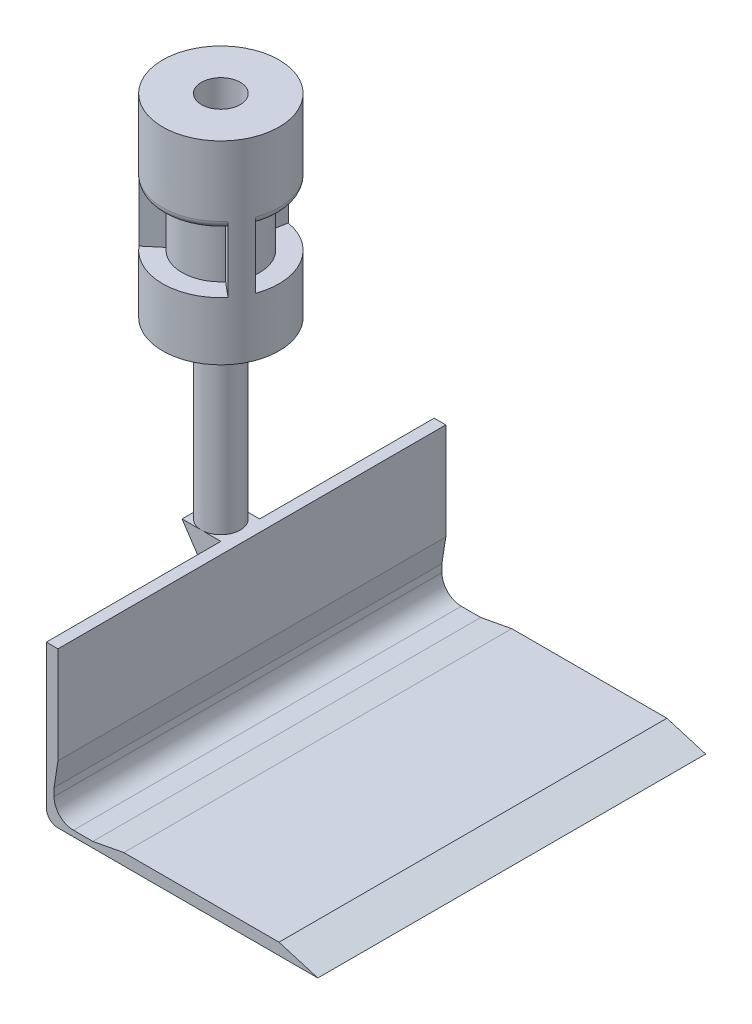
SolidWorks part; units mm, degrees
ref_plane "Front Plane" through (0, 0, 0) normal (0, 0, 1) x (1, 0, 0)
ref_plane "Top Plane" through (0, 0, 0) normal (0, 1, 0) x (1, 0, 0)
ref_plane "Right Plane" through (0, 0, 0) normal (1, 0, 0) x (0, 0, -1)
sketch "Sketch1" plane through (0, 0, 0) normal (0, 0, 1) x (1, 0, 0)
  line L0 (0, 40) -> (0, 15)
  line L2 (-1, 8.5) -> (-1, 6.5)
  line L3 (4, 1.5) -> (9, 1.5)
  line L5 (17, 3) -> (57, 3)
  line L7 (67, 0) -> (-3, 0)
  line L8 (-3, 0) -> (-3, 40)
  line L9 (-3, 40) -> (0, 40)
  line L10 (-1, 8.5) -> (0, 15)
  line L11 (9, 1.5) -> (17, 3)
  line L12 (67, 0) -> (57, 3)
  arc A0 (-1, 6.5) -> (4, 1.5) centre (4, 6.5) ccw
  point P8 (-1, 1.5)
  dimension "D12" = 5
  dimension "D1" = 70
  dimension "D2" = 40
  dimension "D3" = 3
  dimension "D4" = 3
  dimension "D5" = 1.5
  dimension "D6" = 2
  dimension "D7" = 10
  dimension "D8" = 7
  dimension "D9" = 25
  dimension "D10" = 10
  dimension "D11" = 8
extrude "Boss-Extrude1" add sketch "Sketch1" along normal mid plane 100
sketch "Sketch3" plane through (0, 0, 0) normal (0, 0, 1) x (1, 0, 0)
  line L0 (-13, 40) -> (-3, 25)
  line L1 (-3, 40) -> (-3, 0) construction
  line L2 (-3, 25) -> (-3, 40)
  line L4 (-13, 40) -> (-13, 80) construction
  line L5 (-13, 80) -> (-3, 80) construction
  line L6 (-3, 80) -> (-3, 40) construction
  line L7 (-13, 40) -> (-3, 40)
  dimension "D1" = 15
  dimension "D2" = 10
  dimension "D3" = 40
extrude "Boss-Extrude2" add sketch "Sketch3" along normal mid plane 10
sketch "Sketch7" plane through (0, 0, 0) normal (0, 0, 1) x (1, 0, 0)
  line L0 (-8, 40) -> (-8, 87.0793) construction
  line L1 (-3, 40) -> (-13, 40) construction
  line L2 (-8, 40) -> (-3, 40)
  line L3 (-3, 40) -> (-3, 85)
  line L4 (-3, 85) -> (-8, 85)
  line L5 (-8, 85) -> (-8, 40)
  dimension "D1" = 45
revolve "Revolve3" add sketch "Sketch7" angle 360 about L0
ref_plane "Plane1" through (0, 90, 0) normal (0, 1, 0) x (1, 0, 0)
sketch "Sketch5" plane through (0, 0, 0) normal (0, 0, 1) x (1, 0, 0)
  line L0 (-8, 85) -> (-8, 119.3656) construction
  line L1 (-8, 85) -> (-8, 95)
  line L3 (2, 100) -> (2, 115)
  line L4 (7, 135) -> (-3, 135)
  line L5 (-3, 135) -> (-3, 95)
  line L6 (-8, 85) -> (7, 85)
  line L8 (7, 135) -> (7, 115)
  line L9 (7, 115) -> (2, 115)
  line L11 (7, 85) -> (7, 100)
  line L12 (7, 100) -> (2, 100)
  line L13 (-3, 85) -> (-13, 85) construction
  line L14 (-3, 40) -> (-3, 85) construction
  line L15 (-8, 95) -> (-3, 95)
  point P2 (0, 0)
  dimension "D1" = 50
  dimension "D2" = 20
  dimension "D3" = 10
  dimension "D4" = 30
  dimension "D5" = 20
  dimension "D6" = 15
  dimension "D7" = 5
  dimension "D8" = 10
revolve "Revolve2" add sketch "Sketch5" angle 360 about L0
sketch "Sketch6" plane through (0, 100, 0) normal (0, 1, 0) x (1, 0, 0)
  line L0 (-8, 0) -> (-8, 24.9132) construction
  line L1 (-9.3024, 7.3861) -> (-10.6047, 14.7721)
  line L2 (-6.6976, 7.3861) -> (-5.3953, 14.7721)
  line L3 (-8, 0) -> (-10.6047, 14.7721) construction
  line L4 (-0.9523, -2.5652) -> (6.0954, -5.1303)
  line L5 (-2.2547, -4.8209) -> (3.4907, -9.6418)
  line L6 (-13.7453, -4.8209) -> (-19.4907, -9.6418)
  line L7 (-15.0477, -2.5652) -> (-22.0954, -5.1303)
  circle A1 centre (-8, 0) radius 15
  arc A2 (-22.0954, -5.1303) -> (-19.4907, -9.6418) centre (-8, 0) ccw
  arc A3 (-5.3953, 14.7721) -> (-10.6047, 14.7721) centre (-8, 0) ccw
  arc A4 (3.4907, -9.6418) -> (6.0954, -5.1303) centre (-8, 0) ccw
  arc A5 (-15.0477, -2.5652) -> (-13.7453, -4.8209) centre (-8, 0) ccw
  arc A6 (-6.6976, 7.3861) -> (-9.3024, 7.3861) centre (-8, 0) ccw
  arc A7 (-2.2547, -4.8209) -> (-0.9523, -2.5652) centre (-8, 0) ccw
  dimension "D4" = 7.5
  dimension "D2" = 3
  dimension "D3" = 10
  dimension "D1" = 0
extrude "Boss-Extrude3" add sketch "Sketch6" along normal up to next
fillet "Fillet1" radius 2 3 edges at (4.9904, 115, -7.5) (-20.9904, 115, -7.5) (-8, 115, 15)
fillet "Fillet2" radius 3 1 edges at (-3, 0, 0)
